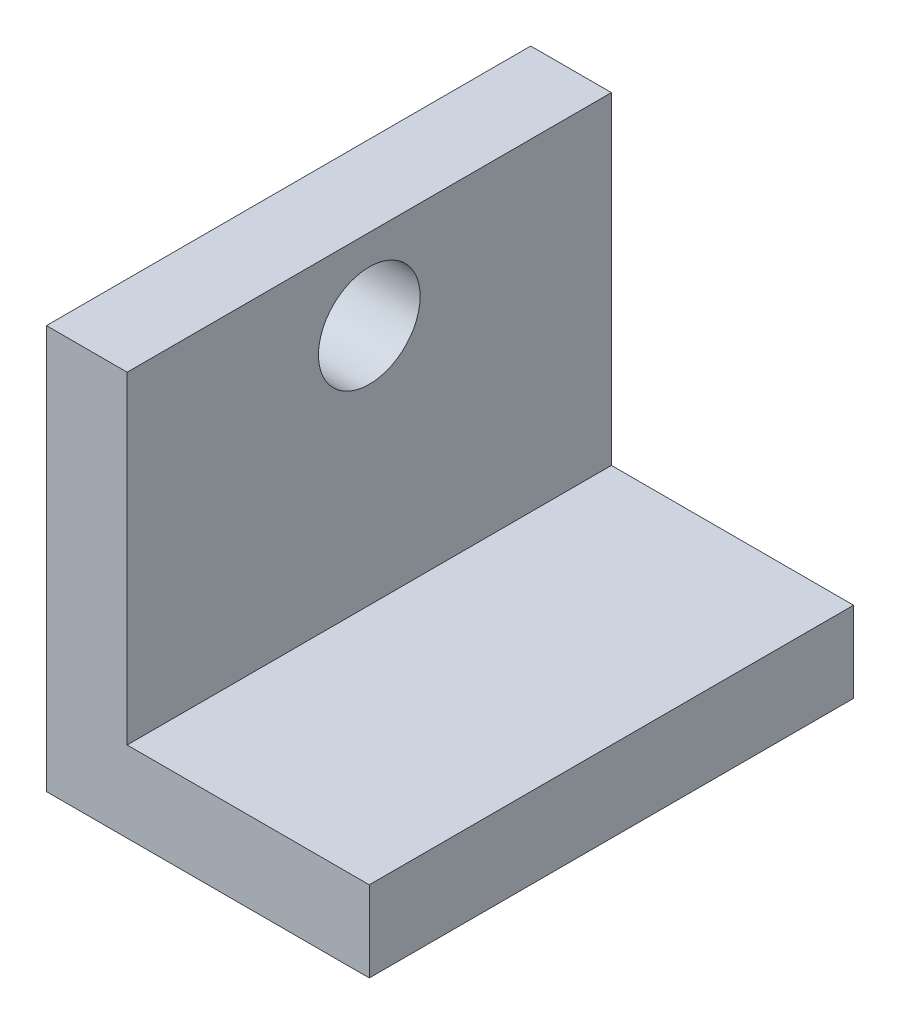
SolidWorks part; units mm, degrees
material "ABS"
ref_plane "Front Plane" through (0, 0, 0) normal (0, 0, 1) x (1, 0, 0)
ref_plane "Top Plane" through (0, 0, 0) normal (0, 1, 0) x (1, 0, 0)
ref_plane "Right Plane" through (0, 0, 0) normal (1, 0, 0) x (0, 0, -1)
sketch "Sketch1" plane through (0, 0, 0) normal (0, 1, 0) x (1, 0, 0)
  line L0 (-3.175, 9.525) -> (-3.175, -9.525)
  line L1 (-6.35, -9.525) -> (6.35, -9.525)
  line L2 (-6.35, -9.525) -> (-6.35, 9.525)
  line L3 (-6.35, 9.525) -> (6.35, 9.525)
  line L4 (6.35, -9.525) -> (6.35, 9.525)
  line L5 (-6.35, -9.525) -> (6.35, 9.525) construction
  line L6 (-6.35, 9.525) -> (6.35, -9.525) construction
  point P0 (0, 0)
  dimension "D1" = 12.7
  dimension "D2" = 3.175
  dimension "D3" = 19.05
extrude "Boss-Extrude1" add sketch "Sketch1" along normal blind 3.175 contours L1 L4 L3 L0 | L3 L2 L1 L0 region at (1.5875, 0, 0) region at (-4.7625, 0, 0)
extrude "Boss-Extrude2" add sketch "Sketch1<3>" along normal blind 12.7 from surface contours L3 L2 L1 L0 region at (-4.7625, 0, 0) starting at face at (0, 3.175, 0)
sketch "Sketch1<3>" plane through (0, 0, 0) normal (0, 1, 0) x (1, 0, 0) same geometry as "Sketch1"
sketch "Sketch2" plane through (-3.175, 0, 0) normal (1, 0, 0) x (0, 0, -1)
  line L0 (0, 15.875) -> (0, 12.7) construction
  line L1 (-9.525, 15.875) -> (9.525, 15.875) construction
  circle A0 centre (0, 12.7) radius 2
  dimension "D1" = 4
  dimension "D2" = 3.175
extrude "Cut-Extrude1" cut sketch "Sketch2" against normal through all
sketch "Sketch3" plane through (-6.35, 0, 0) normal (-1, 0, 0) x (0, 0, 1)
  line L0 (0, 12.7) -> (10.6066, 23.3066) construction
  line L1 (0, 12.7) -> (9.525, 12.7) construction
  line L2 (9.525, 15.875) -> (9.525, 0) construction
  circle A0 centre (0, 12.7) radius 10 construction
  circle A1 centre (10.6066, 23.3066) radius 5 construction
  circle A2 centre (10.6066, 23.3066) radius 12.5 construction
  circle A3 centre (10.6066, 23.3066) radius 12.7
  dimension "D1" = 10
  dimension "D2" = 20
  dimension "D4" = 25
  dimension "D5" = 25.4
  dimension "D3" = 45
extrude "Cut-Extrude2" [suppressed] cut sketch "Sketch3" against normal through all
